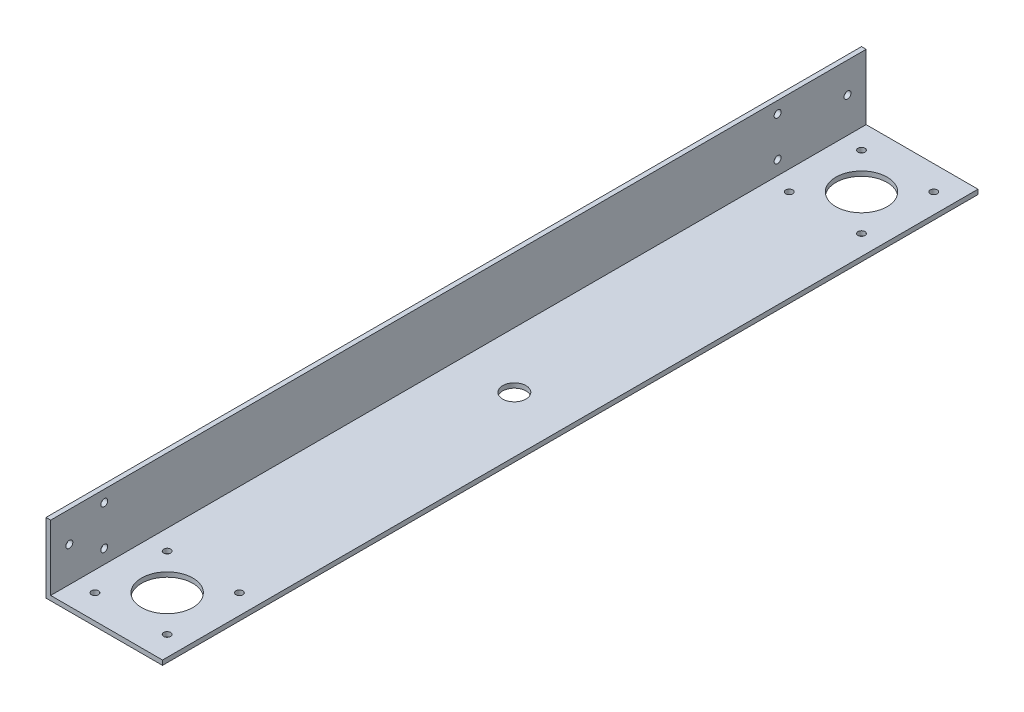
SolidWorks part; units mm, degrees
ref_plane "Front Plane" through (0, 0, 0) normal (0, 0, 1) x (1, 0, 0)
ref_plane "Top Plane" through (0, 0, 0) normal (0, 1, 0) x (1, 0, 0)
ref_plane "Right Plane" through (0, 0, 0) normal (1, 0, 0) x (0, 0, -1)
sketch "Sketch1" plane through (0, 0, 0) normal (0, 0, 1) x (1, 0, 0)
  line L0 (0, 0) -> (0, 30)
  line L1 (0, 30) -> (2, 30)
  line L2 (2, 30) -> (2, 2)
  line L3 (2, 2) -> (50, 2)
  line L4 (50, 2) -> (50, 0)
  line L5 (50, 0) -> (0, 0)
extrude "Boss-Extrude1" add sketch "Sketch1" along normal blind 350
sketch "Sketch6" plane through (0, 2, 0) normal (0, 1, 0) x (1, 0, 0)
  circle A0 centre (41.5, -339.5) radius 1.5
  circle A1 centre (10.5, -308.5) radius 1.5
  circle A2 centre (10.5, -339.5) radius 1.5
  circle A3 centre (41.5, -308.5) radius 1.5
extrude "Cut-Extrude3" cut sketch "Sketch6" against normal through all
sketch "Sketch7" plane through (0, 2, 0) normal (0, 1, 0) x (1, 0, 0)
  circle A0 centre (26, -324) radius 11
extrude "Cut-Extrude4" cut sketch "Sketch7" against normal through all
sketch "Sketch8" plane through (0, 0, 0) normal (0, -1, 0) x (-1, 0, 0)
  circle A0 centre (-26, -26) radius 11
extrude "Cut-Extrude5" cut sketch "Sketch8" against normal through all
sketch "Sketch9" plane through (0, 0, 0) normal (0, -1, 0) x (1, 0, 0)
  circle A0 centre (41.5, 41.5) radius 1.5
  circle A1 centre (10.5, 41.5) radius 1.5
  circle A2 centre (10.5, 10.5) radius 1.5
  circle A3 centre (41.5, 10.5) radius 1.5
extrude "Cut-Extrude6" cut sketch "Sketch9" against normal through all
sketch "Sketch10" plane through (0, 0, 0) normal (0, -1, 0) x (1, 0, 0)
  circle A0 centre (26, 175) radius 5
extrude "Cut-Extrude7" cut sketch "Sketch10" against normal through all
hole_wizard "Ø3.0 (3) Diameter Hole1" positions "Sketch11" profile "Sketch12" hole size "Ø3.0" standard "ISO"
sketch "Sketch11" plane through (0, 141.68, 221.138) normal (-1, 0, 0) x (0, 0, 1)
  point P0 (105.862, -133.68)
  point P1 (120.862, -124.68)
  point P2 (105.862, -116.68)
sketch "Sketch12" plane through (0, 8, 327) normal (0, 1, 0) x (0, 0, 1)
  line L0 (0, 0) -> (0, 1.999)
  line L1 (0, 1.999) -> (1.5, 1.999)
  line L2 (1.5, 1.999) -> (1.5, 0)
  line L3 (1.5, 0) -> (0, 0)
  line L4 (0, -6.35) -> (0, 107.95) construction
  dimension "Thru Hole Dia." = 3
  dimension "Thru Hole Depth" = 1.999
hole_wizard "Ø3.0 (3) Diameter Hole2" positions "Sketch13" profile "Sketch14" hole
sketch "Sketch13" plane through (0, 141.68, 221.138) normal (-1, 0, 0) x (0, 0, 1)
  point P0 (-183.138, -133.68)
  point P1 (-213.138, -124.68)
  point P2 (-183.138, -116.68)
sketch "Sketch14" plane through (0, 8, 38) normal (0, 1, 0) x (0, 0, 1)
  line L0 (0, 0) -> (0, 1.999)
  line L1 (0, 1.999) -> (1.5, 1.999)
  line L2 (1.5, 1.999) -> (1.5, 0)
  line L3 (1.5, 0) -> (0, 0)
  line L4 (0, -6.35) -> (0, 107.95) construction
  dimension "Thru Hole Dia." = 3
  dimension "Thru Hole Depth" = 1.999
